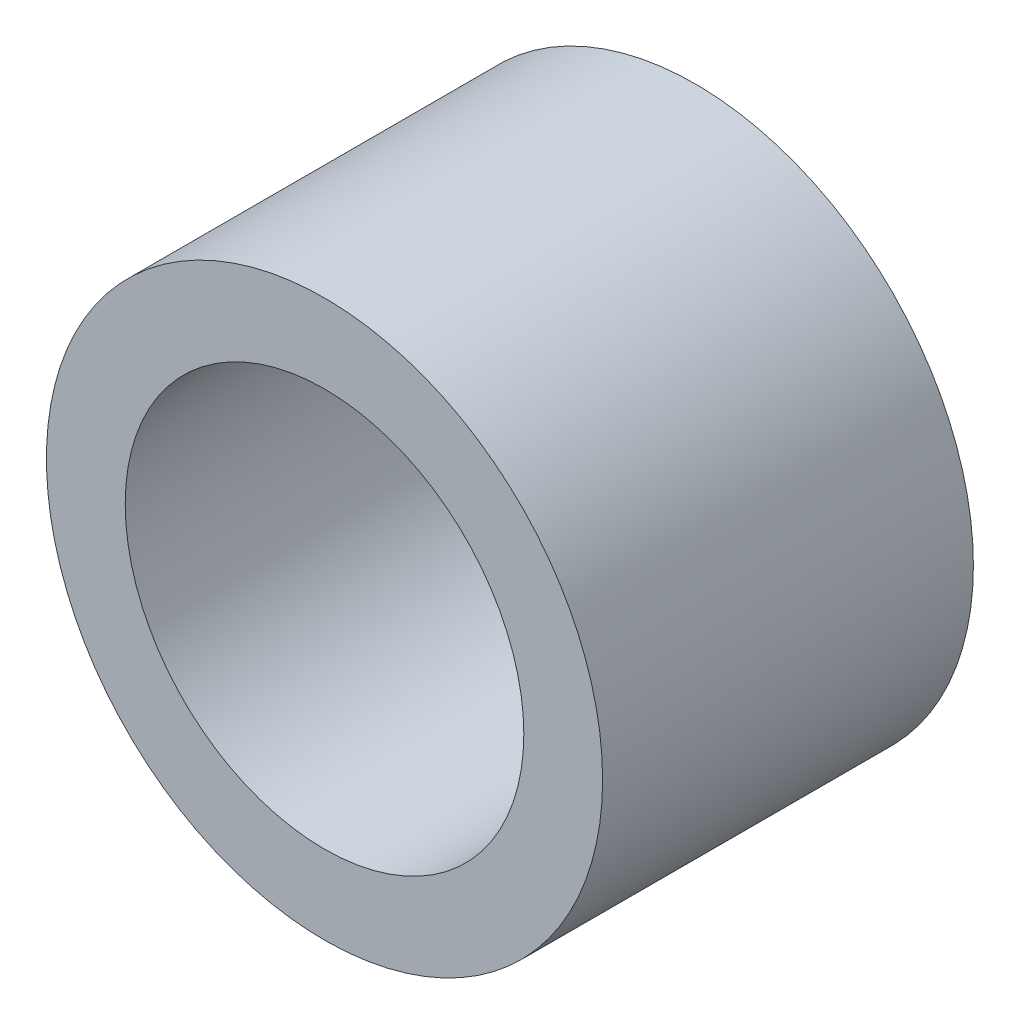
SolidWorks part; units mm, degrees
ref_plane "Front Plane" through (0, 0, 0) normal (0, 0, 1) x (1, 0, 0)
ref_plane "Top Plane" through (0, 0, 0) normal (0, 1, 0) x (1, 0, 0)
ref_plane "Right Plane" through (0, 0, 0) normal (1, 0, 0) x (0, 0, -1)
sketch "Sketch3" plane through (0, 0, 0) normal (0, 0, 1) x (1, 0, 0)
  circle A0 centre (0, 0) radius 2.15 construction
  circle A1 centre (0, 0) radius 3 construction
  point P6 (0, -2.15)
  dimension "OD" = 6
  dimension "ID" = 4.3
sketch "Sketch1" plane through (0, 0, 0) normal (1, 0, 0) x (0, 0, -1)
  line L0 (-2, -2.15) -> (-2, 2.15) construction
  line L1 (2, -3) -> (-2, -3) construction
  line L2 (2, -3) -> (2, 3) construction
  line L3 (2, 3) -> (-2, 3) construction
  line L4 (-2, -3) -> (-2, 3) construction
  line L5 (0, 3) -> (0, -3) construction
  line L6 (2, 0) -> (-2, 0) construction
  point P0 (0, 0)
  point P7 (-2, 0)
  dimension "OD" = 6
  dimension "ID" = 4.3
sketch "Sketch2" plane through (0, 0, 0) normal (0, 0, 1) x (1, 0, 0)
  circle A0 centre (0, 0) radius 3
  circle A1 centre (0, 0) radius 2.15
extrude "Extrude1" add sketch "Sketch2" along normal up to vertex and the other way up to vertex up to point (0, -3, 2) other way up to point (0, 3, -2)
equation "\"ID@Sketch1\" = \"ID@Sketch3\""
equation "\"OD@Sketch1\" = \"OD@Sketch3\""
